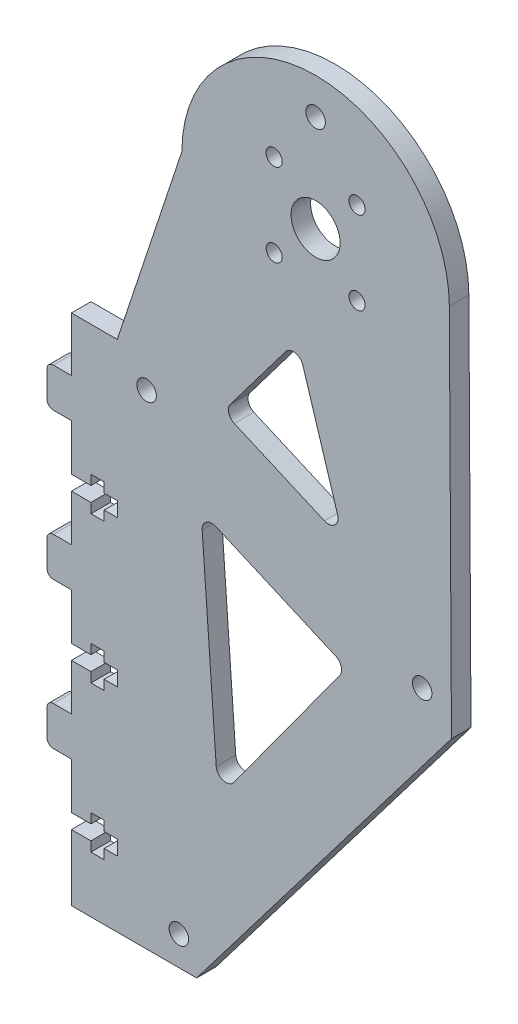
SolidWorks part; units mm, degrees
ref_plane "前视基准面" through (0, 0, 0) normal (0, 0, 1) x (1, 0, 0)
ref_plane "上视基准面" through (0, 0, 0) normal (0, 1, 0) x (1, 0, 0)
ref_plane "右视基准面" through (0, 0, 0) normal (1, 0, 0) x (0, 0, -1)
sketch "草图1" plane through (0, 0, 0) normal (0, 0, 1) x (1, 0, 0)
  line L4 (348.5429, 4.8543) -> (428.5429, 4.8543) construction
  line L11 (348.5429, 4.8543) -> (298.5429, 4.8543) construction
  line L15 (298.5515, -96.6457) -> (302.5515, -96.6457)
  line L16 (302.5515, -96.6457) -> (302.5515, -98.6442)
  line L17 (302.5515, -98.6442) -> (305.2515, -98.6442)
  line L18 (305.2515, -98.6442) -> (305.2515, -96.6457)
  line L19 (305.2515, -96.6457) -> (307.9515, -96.6457)
  line L20 (307.9515, -96.6457) -> (307.9515, -93.6457)
  line L21 (307.9515, -93.6457) -> (305.2515, -93.6457)
  line L22 (305.2515, -93.6457) -> (305.2515, -91.6472)
  line L23 (305.2515, -91.6472) -> (302.5515, -91.6472)
  line L24 (302.5515, -91.6472) -> (302.5515, -93.6457)
  line L25 (302.5515, -93.6457) -> (298.5515, -93.6457)
  line L27 (298.5429, -95.1457) -> (302.5429, -95.1457) construction
  line L28 (298.5515, -110.1457) -> (303.5515, -110.1457) construction
  line L29 (303.5515, -114.1457) -> (293.5515, -114.1457) construction
  line L30 (303.5515, -114.1457) -> (303.5515, -106.1457) construction
  line L31 (303.5515, -106.1457) -> (293.5515, -106.1457) construction
  line L32 (293.5515, -114.1457) -> (293.5515, -106.1457)
  line L33 (303.5515, -114.1457) -> (293.5515, -106.1457) construction
  line L34 (303.5515, -106.1457) -> (293.5515, -114.1457) construction
  line L35 (302.5515, -126.6457) -> (298.5515, -126.6457)
  line L36 (298.5515, -123.6457) -> (302.5515, -123.6457)
  line L37 (302.5515, -128.6442) -> (302.5515, -126.6457)
  line L38 (305.2515, -128.6442) -> (302.5515, -128.6442)
  line L39 (305.2515, -126.6457) -> (305.2515, -128.6442)
  line L40 (307.9515, -126.6457) -> (305.2515, -126.6457)
  line L41 (307.9515, -123.6457) -> (307.9515, -126.6457)
  line L42 (305.2515, -123.6457) -> (307.9515, -123.6457)
  line L43 (305.2515, -121.6473) -> (305.2515, -123.6457)
  line L44 (302.5515, -121.6473) -> (305.2515, -121.6473)
  line L45 (302.5515, -123.6457) -> (302.5515, -121.6473)
  line L46 (293.5515, -76.1457) -> (293.5515, -84.1457)
  line L47 (302.5515, -63.6457) -> (298.5515, -63.6457)
  line L48 (298.5515, -66.6457) -> (302.5515, -66.6457)
  line L49 (302.5515, -66.6457) -> (302.5515, -68.6442)
  line L50 (302.5515, -68.6442) -> (305.2515, -68.6442)
  line L51 (305.2515, -68.6442) -> (305.2515, -66.6457)
  line L52 (305.2515, -66.6457) -> (307.9515, -66.6457)
  line L53 (307.9515, -66.6457) -> (307.9515, -63.6457)
  line L54 (307.9515, -63.6457) -> (305.2515, -63.6457)
  line L55 (305.2515, -63.6457) -> (305.2515, -61.6472)
  line L56 (305.2515, -61.6472) -> (302.5515, -61.6472)
  line L57 (302.5515, -61.6472) -> (302.5515, -63.6457)
  line L58 (293.5515, -84.1457) -> (298.5515, -84.1457)
  line L59 (293.5515, -76.1457) -> (298.5515, -76.1457)
  line L60 (298.5515, -76.1457) -> (298.5515, -66.6457)
  line L61 (298.5515, -84.1457) -> (298.5515, -93.6457)
  line L62 (298.5515, -96.6457) -> (298.5515, -106.1457)
  line L63 (298.5515, -106.1457) -> (293.5515, -106.1457)
  line L64 (293.5515, -114.1457) -> (298.5515, -114.1457)
  line L65 (298.5515, -114.1457) -> (298.5515, -123.6457)
  line L66 (307.9515, -65.1457) -> (305.2429, -65.1457) construction
  line L67 (293.5515, -46.1457) -> (298.5515, -46.1457)
  line L68 (293.5515, -54.1457) -> (293.5515, -46.1457)
  line L69 (293.5515, -54.1457) -> (298.5515, -54.1457)
  line L70 (298.5515, -54.1457) -> (298.5515, -63.6457)
  line L78 (298.5515, -126.6457) -> (298.5515, -140.1457)
  line L79 (298.5515, -140.1457) -> (324.1947, -140.1457)
  line L81 (375.9264, 4.8543) -> (376.3645, -71.6457)
  line L84 (376.3645, -71.6457) -> (324.1947, -140.1457)
  line L85 (298.5515, -46.1457) -> (298.5515, -35.0457)
  line L87 (298.5515, -35.0457) -> (307.9429, -35.0457)
  line L88 (307.9429, -35.0457) -> (321.1593, 4.8543)
  line L89 (320.5515, -134.1457) -> (313.9429, -41.0457) construction
  line L90 (313.9429, -41.0457) -> (370.3645, -65.6457) construction
  line L91 (370.3645, -65.6457) -> (320.5515, -134.1457) construction
  line L92 (354.9532, -69.8355) -> (328.5855, -106.0948)
  line L93 (328.5855, -106.0948) -> (325.0873, -56.8139)
  line L94 (325.0873, -56.8139) -> (354.9532, -69.8355)
  line L95 (370.3645, -65.6457) -> (348.5429, 4.6975) construction
  line L96 (348.5429, 4.6975) -> (313.9429, -41.0457) construction
  line L97 (329.577, -36.9531) -> (354.3432, -47.7512)
  line L98 (354.3432, -47.7512) -> (344.7646, -16.8742)
  line L99 (344.7646, -16.8742) -> (329.577, -36.9531)
  line L100 (348.5429, 4.8543) -> (336.9755, 16.4217) construction
  line L101 (348.5429, 4.8543) -> (428.5429, 4.8543) construction
  line L102 (428.5429, 14.8543) -> (370.3645, 21.2413) construction
  line L103 (428.5429, -5.1457) -> (370.3645, -11.6888) construction
  line L104 (376.3645, -71.6457) -> (376.0175, -11.0531) construction
  line L105 (376.0175, -11.0531) -> (428.5429, -5.1457) construction
  circle A11 centre (348.5429, 4.8543) radius 5.0225
  circle A14 centre (348.5429, 4.8543) radius 27.3835 construction
  arc A22 (375.9264, 4.8543) -> (321.1593, 4.8543) centre (348.5429, 4.6975) ccw
  circle A23 centre (348.5429, 24.6975) radius 2
  circle A24 centre (320.5515, -134.1457) radius 2
  circle A25 centre (370.3645, -65.6457) radius 2
  circle A26 centre (313.9429, -41.0457) radius 2
  circle A27 centre (348.5429, 4.8543) radius 12 construction
  circle A28 centre (340.0576, 13.3396) radius 1.65
  circle A29 centre (357.0281, 13.3396) radius 1.65
  circle A30 centre (357.0281, -3.631) radius 1.65
  circle A31 centre (340.0576, -3.631) radius 1.65
  circle A32 centre (428.5429, 4.8543) radius 5 construction
  circle A33 centre (428.5429, 4.8543) radius 10 construction
  arc A34 (428.5429, 14.8543) -> (428.5429, -5.1457) centre (428.5429, 4.8543) cw construction
  arc A35 (321.1593, 4.8543) -> (370.3645, 21.2413) centre (348.5429, 4.6975) cw construction
  point P30 (298.5515, -110.1457)
  dimension "D2" = 20
  dimension "D3" = 3
  dimension "D4" = 10.045
  dimension "D5" = 2.7
  dimension "D6" = 50
  dimension "D15" = 22
  dimension "D17" = 6
  dimension "D19" = 6
  dimension "D23" = 24
  dimension "D25" = 3.3
  dimension "D28" = 10
  dimension "D29" = 20
  dimension "D7" = 80
  dimension "D8" = 4
  dimension "D9" = 1.5
  dimension "D10" = 15
  dimension "D11" = 8
  dimension "D12" = 10
  dimension "D13" = 100
  dimension "D14" = 13.5
  dimension "D16" = 6
  dimension "D18" = 6
  dimension "D20" = 6
  dimension "D24" = 45
  dimension "D27" = 80
  dimension "D21" = 10
  dimension "D22" = 10
  dimension "D26" = 4
extrude "凸台-拉伸1" add sketch "草图1" along normal blind 4
sketch "草图2" plane through (298.5515, 0, 0) normal (-1, 0, 0) x (0, 0, 1)
  line L0 (2, -66.6457) -> (2, -63.6457)
  line L1 (4, -66.6457) -> (0, -66.6457) construction
  line L2 (4, -63.6457) -> (0, -63.6457) construction
  circle A0 centre (2, -65.1457) radius 1.5
fillet "圆角1" radius 2 6 edges at (344.7646, -16.8742, 2) (329.577, -36.9531, 2) (354.3432, -47.7512, 2) (325.0873, -56.8139, 2) (328.5855, -106.0948, 2) (354.9532, -69.8355, 2)
fillet "圆角2" radius 1.3 6 edges at (293.5515, -46.1457, 2) (293.5515, -54.1457, 2) (293.5515, -84.1457, 2) (293.5515, -76.1457, 2) (293.5515, -114.1457, 2) (293.5515, -106.1457, 2)
